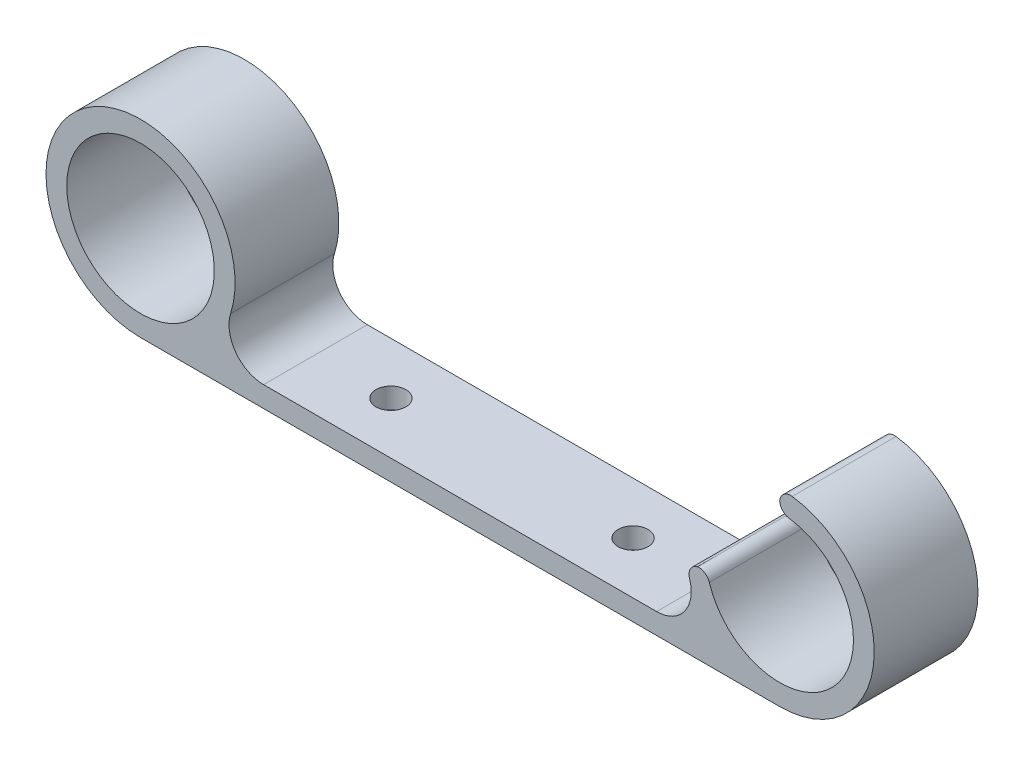
SolidWorks part; units mm, degrees
ref_plane "Front Plane" through (0, 0, 0) normal (0, 0, 1) x (1, 0, 0)
ref_plane "Top Plane" through (0, 0, 0) normal (0, 1, 0) x (1, 0, 0)
ref_plane "Right Plane" through (0, 0, 0) normal (1, 0, 0) x (0, 0, -1)
sketch "Sketch3" plane through (0, 0, 0) normal (0, 1, 0) x (1, 0, 0)
  line L1 (-57.15, -9.525) -> (57.15, -9.525)
  line L2 (-57.15, -9.525) -> (-57.15, 9.525)
  line L3 (-57.15, 9.525) -> (57.15, 9.525)
  line L4 (57.15, -9.525) -> (57.15, 9.525)
  line L5 (-57.15, -9.525) -> (57.15, 9.525) construction
  line L6 (-57.15, 9.525) -> (57.15, -9.525) construction
  point P0 (0, 0)
  dimension "D1" = 19.05
  dimension "D2" = 114.3
extrude "Boss-Extrude1" add sketch "Sketch3" along normal blind 3.81
sketch "Sketch4" plane through (0, 0, 0) normal (0, 0, 1) x (1, 0, 0)
  line L0 (-58.6588, 17.3553) -> (58.6588, 17.3553) construction
  line L1 (57.15, 3.81) -> (-57.15, 3.81) construction
  line L2 (0, -20.955) -> (0, 20.955) construction
  line L5 (20.955, 0) -> (-20.955, 0) construction
  line L8 (-57.15, 3.81) -> (57.15, 3.81) construction
  line L9 (-36.0719, 3.81) -> (36.0719, 3.81)
  line L11 (-57.15, 0) -> (57.15, 0) construction
  line L12 (74.7593, 0) -> (-74.7593, 0) construction
  line L13 (0, 3.81) -> (0, 0)
  line L14 (58.6588, 0) -> (-58.6588, 0)
  line L16 (58.6588, 17.3553) -> (41.5671, 14.3416) construction
  line L17 (58.6588, 17.3553) -> (58.6588, 34.7106) construction
  line L18 (58.6588, 17.3553) -> (64.5947, 33.664) construction
  line L19 (41.5671, 14.3416) -> (45.3193, 15.0032)
  line L20 (58.6588, 34.7106) -> (58.6588, 30.9006)
  circle A0 centre (-58.6588, 17.3553) radius 13.5453
  arc A1 (45.3193, 15.0032) -> (63.2916, 30.0837) centre (58.6588, 17.3553) ccw
  arc A2 (-42.1223, 12.0874) -> (-76.0141, 17.3553) centre (-58.6588, 17.3553) ccw
  arc A3 (42.1223, 12.0874) -> (41.5671, 14.3416) centre (58.6588, 17.3553) cw
  arc A4 (-36.0719, 3.81) -> (-42.1223, 12.0874) centre (-36.0719, 10.16) cw
  arc A5 (36.0719, 3.81) -> (42.1223, 12.0874) centre (36.0719, 10.16) ccw
  arc A6 (42.1223, 12.0874) -> (41.5671, 14.3416) centre (58.6588, 17.3553) cw
  arc A7 (-42.1223, 12.0874) -> (-76.0141, 17.3553) centre (-58.6588, 17.3553) ccw
  arc A8 (41.5671, 14.3416) -> (42.1223, 12.0874) centre (58.6588, 17.3553) ccw
  arc A9 (64.5947, 33.664) -> (76.0141, 17.3553) centre (58.6588, 17.3553) cw
  arc A10 (64.5947, 33.664) -> (76.0141, 17.3553) centre (58.6588, 17.3553) cw
  arc A11 (58.6588, 0) -> (64.5947, 33.664) centre (58.6588, 17.3553) ccw
  arc A12 (63.2916, 30.0837) -> (58.6588, 30.9006) centre (58.6588, 17.3553) ccw
  arc A13 (64.5947, 33.664) -> (58.6588, 34.7106) centre (58.6588, 17.3553) ccw
  arc A15 (-76.0141, 17.3553) -> (-58.6588, 0) centre (-58.6588, 17.3553) ccw
  point P6 (0, 17.3553)
  point P28 (-47.8084, 3.81)
  dimension "D1" = 27.0906
  dimension "D4" = 3.81
  dimension "D5" = 6.35
  dimension "D2" = 117.3176
  dimension "D6" = 100
  dimension "D7" = 20
sketch "Sketch5" plane through (0, 3.81, 0) normal (0, 1, 0) x (1, 0, 0)
  line L1 (57.15, 9.525) -> (-57.15, 9.525) construction
  line L2 (0, 13.545) -> (0, 9.525) construction
  line L3 (-2.0955, 0) -> (2.0955, 0) construction
  line L4 (0, -13.545) -> (0, -9.525) construction
  line L7 (0, -2.0955) -> (0, 2.0955) construction
  circle A6 centre (-22.225, 0) radius 2.75
  circle A7 centre (22.225, 0) radius 2.75
  dimension "D2" = 44.45
  dimension "D1" = 5.5
extrude "Boss-Extrude2" add sketch "Sketch4" along normal mid plane 19.05 contours A0 A2 L12 L13 L9 A4 | A5 L9 L13 L12 A6 A1 A3 region at (-18.0359, 2.9744, 0) region at (46.8476, 8.7031, 0)
fillet "Fillet1" radius 2.032 4 edges at (58.6588, 34.7106, 0) (58.6588, 30.9006, 0) (45.3193, 15.0032, 0) (41.5671, 14.3416, 0)
extrude "Cut-Extrude4" cut sketch "Sketch5" against normal blind 12.7
